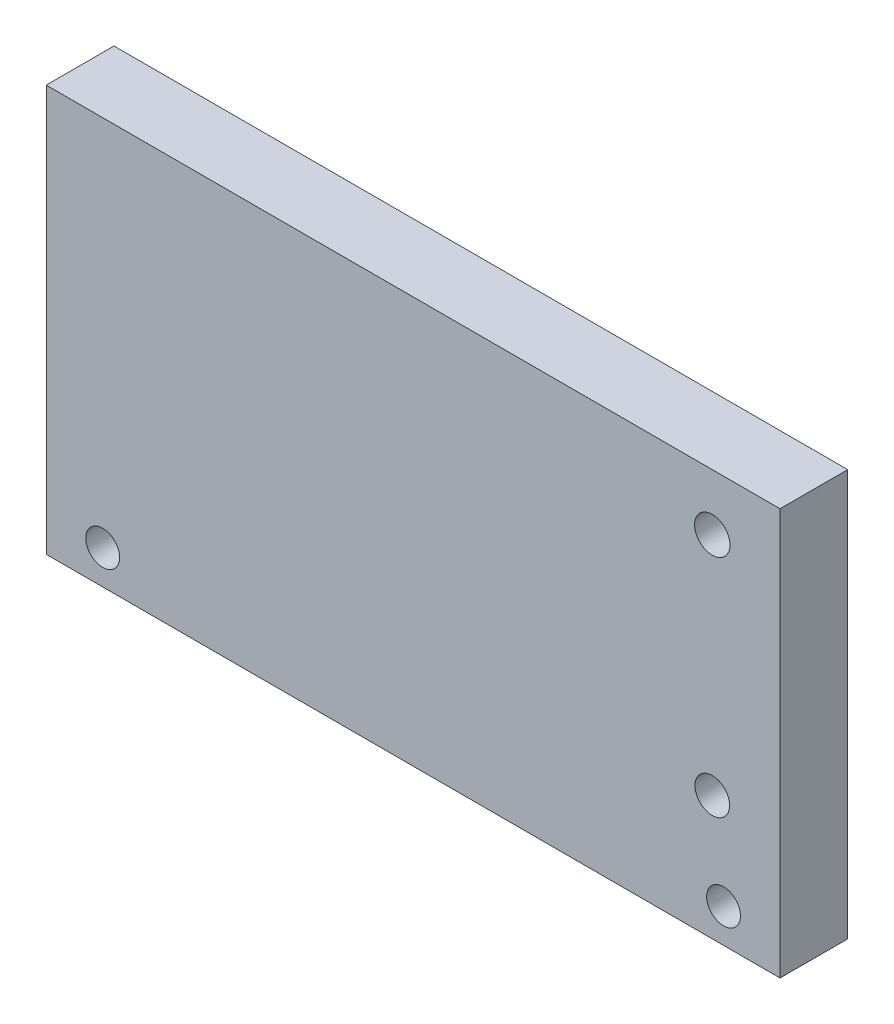
SolidWorks part; units mm, degrees
ref_plane "Plan de face" through (0, 0, 0) normal (0, 0, 1) x (1, 0, 0)
ref_plane "Plan de dessus" through (0, 0, 0) normal (0, 1, 0) x (1, 0, 0)
ref_plane "Plan de droite" through (0, 0, 0) normal (1, 0, 0) x (0, 0, -1)
sketch "Esquisse1" plane through (0, 0, 0) normal (0, 0, 1) x (1, 0, 0)
  line L1 (-40.2712, 36.6319) -> (24.7288, 36.6319)
  line L2 (-40.2712, 36.6319) -> (-40.2712, 0.6319)
  line L3 (-40.2712, 0.6319) -> (24.7288, 0.6319)
  line L4 (24.7288, 36.6319) -> (24.7288, 0.6319)
  circle A0 centre (18.7288, 31.6319) radius 1.5672
  circle A1 centre (18.7288, 11.6319) radius 1.5343
  dimension "D1" = 65
  dimension "D2" = 36
  dimension "D3" = 5
  dimension "D4" = 25
  dimension "D5" = 6
  dimension "D6" = 6
extrude "Boss.-Extru.1" add sketch "Esquisse1" along normal blind 6
sketch "Esquisse3" plane through (0, 0, 6) normal (0, 0, 1) x (1, 0, 0)
  line L0 (-40.2712, 0.6319) -> (24.7288, 0.6319) construction
  line L2 (24.7288, 0.6319) -> (24.7288, 36.6319) construction
  line L3 (-40.2712, 36.6319) -> (-40.2712, 0.6319) construction
  circle A0 centre (-35.2712, 3.6319) radius 1.5
  circle A1 centre (19.7288, 3.6319) radius 1.5
  dimension "D1" = 3
  dimension "D2" = 3
  dimension "D3" = 5
  dimension "D4" = 3
  dimension "D5" = 5
extrude "Enlèv. mat.-Extru.1" cut sketch "Esquisse3" against normal blind 10
